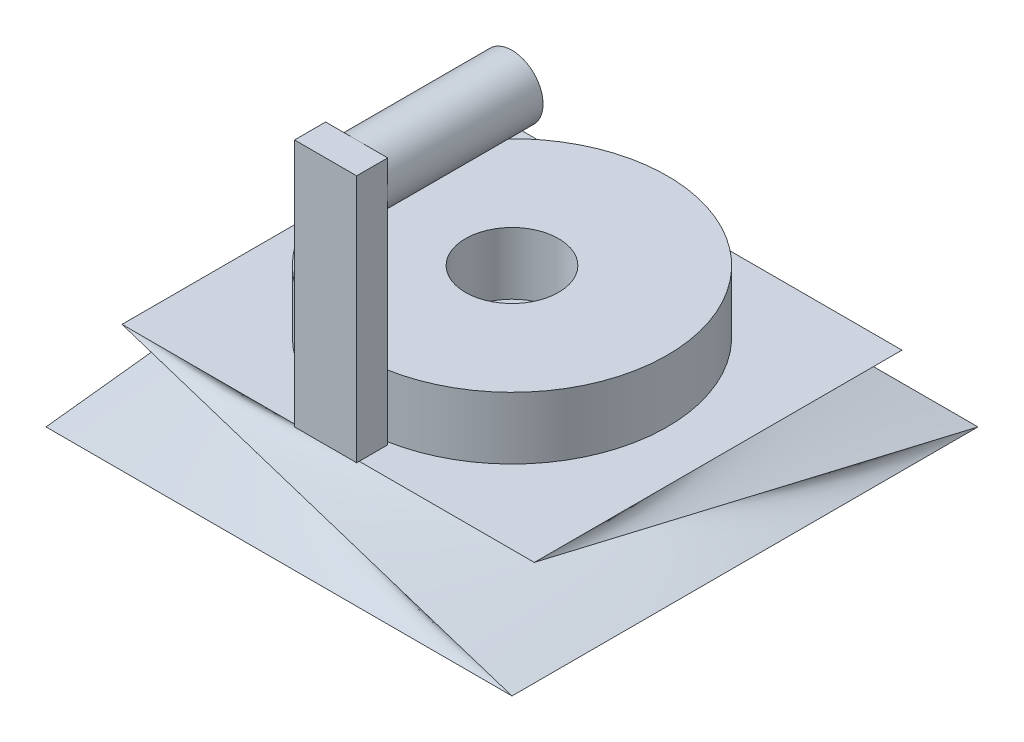
SolidWorks part; units mm, degrees
ref_plane "Front Plane" through (0, 0, 0) normal (0, 0, 1) x (1, 0, 0)
ref_plane "Top Plane" through (0, 0, 0) normal (0, 1, 0) x (1, 0, 0)
ref_plane "Right Plane" through (0, 0, 0) normal (1, 0, 0) x (0, 0, -1)
sketch "Sketch1" plane through (0, 0, 0) normal (0, 1, 0) x (1, 0, 0)
  circle A0 centre (0, 0) radius 15
  circle A1 centre (0, 0) radius 50
  dimension "D1" = 100
  dimension "D2" = 30
extrude "Boss-Extrude1" add sketch "Sketch1" along normal blind 20
sketch "Sketch2" plane through (0, 0, 0) normal (0, -1, 0) x (1, 0, 0)
  line L1 (-66.3612, 59.1739) -> (66.3612, 59.1739)
  line L2 (-66.3612, 59.1739) -> (-66.3612, -59.1739)
  line L3 (-66.3612, -59.1739) -> (66.3612, -59.1739)
  line L4 (66.3612, 59.1739) -> (66.3612, -59.1739)
  line L5 (-66.3612, 59.1739) -> (66.3612, -59.1739) construction
  line L6 (-66.3612, -59.1739) -> (66.3612, 59.1739) construction
  point P0 (0, 0)
ref_plane "Plane1" through (0, -25, 0) normal (0, -1, 0) x (-1, 0, 0)
sketch "Sketch3" plane through (0, -25, 0) normal (0, -1, 0) x (-1, 0, 0)
  line L1 (-75, 75) -> (75, 75)
  line L2 (-75, 75) -> (-75, -75)
  line L3 (-75, -75) -> (75, -75)
  line L4 (75, 75) -> (75, -75)
  line L5 (-75, 75) -> (75, -75) construction
  line L6 (-75, -75) -> (75, 75) construction
  point P0 (0, 0)
  point P5 (0, 0)
  point P6 (0, 0)
  dimension "D1" = 150
  dimension "D2" = 150
loft "Loft1" add profiles "Sketch2", "Sketch3" connector at (66.3612, 0, 59.1739) connector at (75, -25, -75)
sketch "Sketch4" plane through (0, 0, 0) normal (0, 1, 0) x (1, 0, 0)
  line L0 (0, 0) -> (0, -50)
  line L1 (-66.3612, 59.1739) -> (66.3612, -59.1739) construction
  dimension "D1" = 50
ref_axis "Axis1" through (0, 0, 0) along (0, 0, 1)
ref_plane "Plane2" through (0, 0, 50) normal (0, 0, 1) x (1, 0, 0)
sketch "Sketch6" plane through (0, 0, 50) normal (0, 0, 1) x (1, 0, 0)
  line L1 (-10, 80) -> (10, 80)
  line L2 (-10, 80) -> (-10, 0)
  line L3 (-10, 0) -> (10, 0)
  line L4 (10, 80) -> (10, 0)
  line L5 (-10, 80) -> (10, 0) construction
  line L6 (-10, 0) -> (10, 80) construction
  point P0 (0, 40)
  dimension "D1" = 80
  dimension "D2" = 20
extrude "Boss-Extrude7" add sketch "Sketch6" along normal blind 10 separate body
sketch "Sketch7" plane through (0, 0, 50) normal (0, 0, -1) x (-1, 0, 0)
  line L0 (-10, 80) -> (10, 80) construction
  line L1 (10, 80) -> (10, 0) construction
  circle A0 centre (0, 70) radius 10
  point P2 (0, 0)
  dimension "D1" = 20
extrude "Boss-Extrude8" add sketch "Sketch7" along normal blind 50 contours A0
